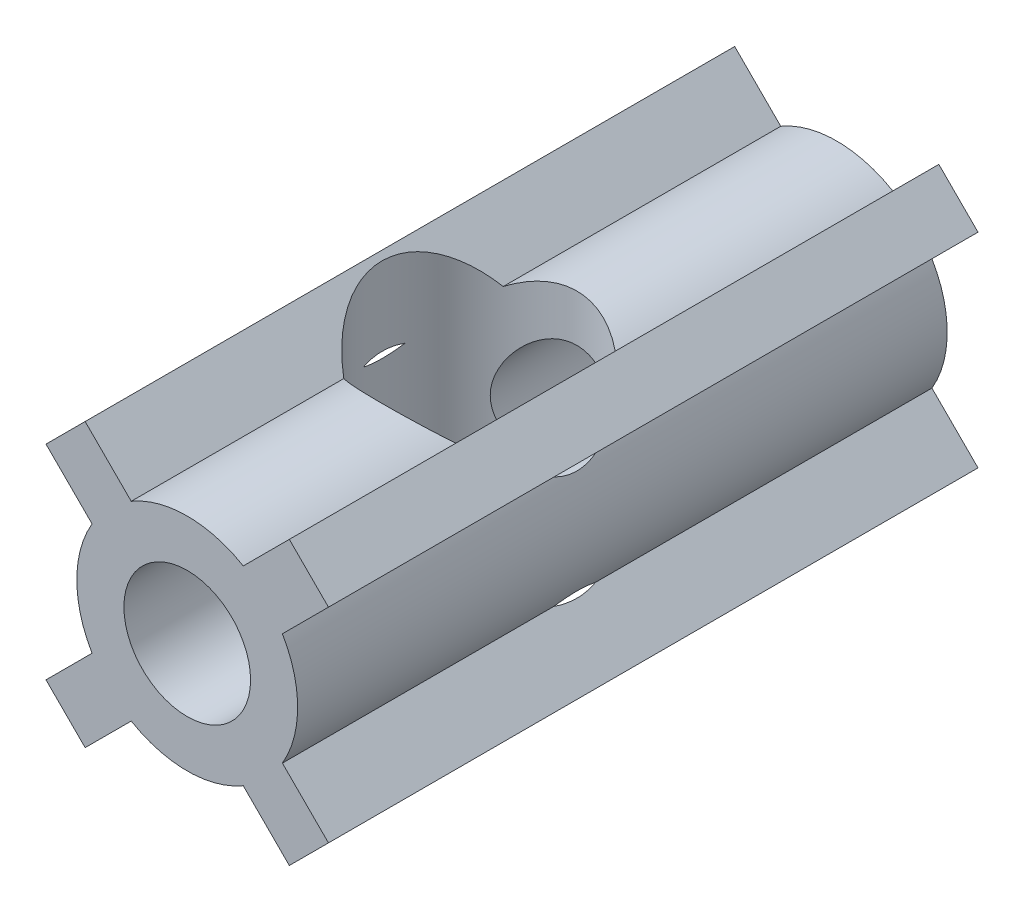
SolidWorks part; units mm, degrees
ref_plane "Front Plane" through (0, 0, 0) normal (0, 0, 1) x (1, 0, 0)
ref_plane "Top Plane" through (0, 0, 0) normal (0, 1, 0) x (1, 0, 0)
ref_plane "Right Plane" through (0, 0, 0) normal (1, 0, 0) x (0, 0, -1)
sketch "Sketch1" plane through (0, 0, 0) normal (0, 0, 1) x (1, 0, 0)
  line L12 (3.1431, 4.3487) -> (4.3487, 3.1431)
  line L13 (4.3487, 3.1431) -> (2.9302, 1.7246)
  line L14 (2.9302, -1.7246) -> (4.3487, -3.1431)
  line L15 (4.3487, -3.1431) -> (3.1431, -4.3487)
  line L16 (3.1431, -4.3487) -> (1.7246, -2.9302)
  line L17 (-3.1431, -4.3487) -> (-1.7246, -2.9302)
  line L18 (-4.3487, -3.1431) -> (-3.1431, -4.3487)
  line L19 (-2.9302, -1.7246) -> (-4.3487, -3.1431)
  line L20 (-4.3487, 3.1431) -> (-2.9302, 1.7246)
  line L21 (-3.1431, 4.3487) -> (-4.3487, 3.1431)
  line L22 (-1.7246, 2.9302) -> (-3.1431, 4.3487)
  line L23 (1.7246, 2.9302) -> (3.1431, 4.3487)
  arc A4 (2.9302, 1.7246) -> (2.9302, -1.7246) centre (0, 0) cw
  arc A5 (-1.7246, -2.9302) -> (1.7246, -2.9302) centre (0, 0) ccw
  arc A6 (-2.9302, 1.7246) -> (-2.9302, -1.7246) centre (0, 0) ccw
  arc A7 (1.7246, 2.9302) -> (-1.7246, 2.9302) centre (0, 0) ccw
  circle A8 centre (0, 0) radius 1.95
extrude "Boss-Extrude1" add sketch "Sketch1" along normal blind 20
sketch "Sketch2" plane through (0, 0, 0) normal (0, 1, 0) x (1, 0, 0)
  circle A0 centre (0, -11) radius 3
extrude "Cut-Extrude1" cut sketch "Sketch2" against normal blind 20 and the other way blind 20
